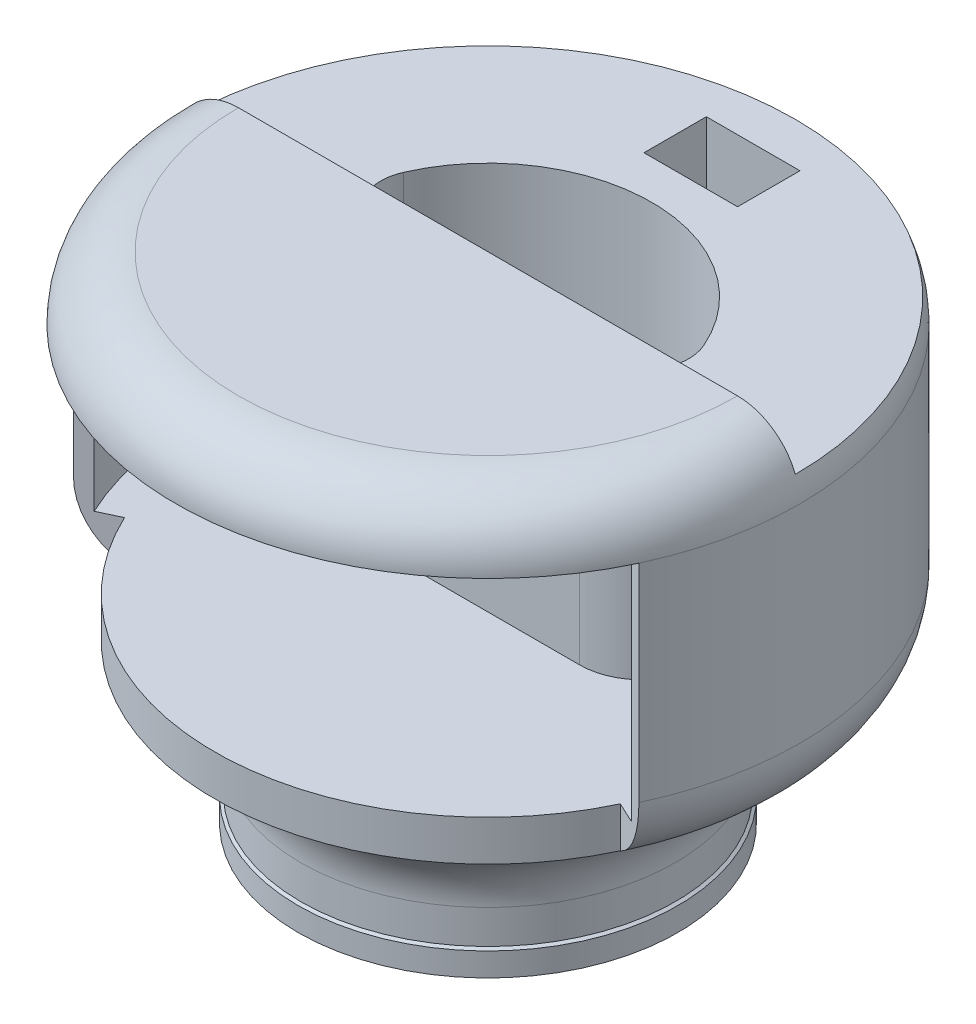
SolidWorks part; units mm, degrees
ref_plane "Front Plane" through (0, 0, 0) normal (0, 0, 1) x (1, 0, 0)
ref_plane "Top Plane" through (0, 0, 0) normal (0, 1, 0) x (1, 0, 0)
ref_plane "Right Plane" through (0, 0, 0) normal (1, 0, 0) x (0, 0, -1)
sketch "Sketch1" plane through (0, 0, 0) normal (0, 0, 1) x (1, 0, 0)
  line L0 (0, 0) -> (0, 90.2242) construction
  line L28 (0, 63.4279) -> (32, 63.4279)
  line L29 (40, 55.4279) -> (40, 28.8468)
  line L30 (22.5, 0) -> (24.35, 0)
  line L31 (24.35, 0) -> (24.35, 3)
  line L32 (24.35, 3) -> (24, 3.25)
  line L33 (24, 3.25) -> (24, 7.5811)
  line L34 (28.5399, 15.9588) -> (35.4601, 20.4691)
  line L35 (0, 13) -> (22, 13)
  line L36 (22.5, 12.5) -> (22.5, 0)
  line L37 (0, 13) -> (0, 63.4279)
  arc A0 (22, 13) -> (22.5, 12.5) centre (22, 12.5) cw
  arc A1 (24, 7.5811) -> (28.5399, 15.9588) centre (34, 7.5811) cw
  arc A2 (35.4601, 20.4691) -> (40, 28.8468) centre (30, 28.8468) ccw
  arc A3 (32, 63.4279) -> (40, 55.4279) centre (32, 55.4279) cw
  point P11 (22.9, 63.4279)
  point P18 (22.5, 13)
  point P21 (24, 13)
  point P24 (40, 23.4279)
  point P27 (40, 63.4279)
  point P28 (28.5604, 23.4279)
  point P31 (22.5, 17)
  dimension "D8" = 9.75
  dimension "D9" = 0.5
  dimension "D4" = 1.85
  dimension "D1" = 22.5
  dimension "D10" = 10
  dimension "D11" = 10
  dimension "D12" = 8
  dimension "D2" = 40
  dimension "D3" = 40
  dimension "D5" = 1.5
  dimension "D6" = 3
  dimension "D7" = 13
revolve "Revolve1" add sketch "Sketch1" angle 360 about L0
ref_plane "Plane1" through (0, 13, 0) normal (0, -1, 0) x (-1, 0, 0)
sketch "Sketch18" plane through (0, 0, 0) normal (0, 0, 1) x (1, 0, 0)
  line L0 (0, 0) -> (0, 101.5813) construction
  line L1 (-24.35, 0) -> (24.35, 0) construction
sketch "Sketch3" plane through (0, 0, 0) normal (0, 0, 1) x (1, 0, 0)
  point P0 (1.2404, 19.1989)
ref_point "Point1"
ref_plane "Plane2" through (0, 0, 22.9) normal (0, 0, 1) x (1, 0, 0)
ref_plane "Plane3" through (0, 0, 40) normal (0, 0, 1) x (1, 0, 0)
ref_plane "Plane4" through (0, 55.4279, 0) normal (0, 1, 0) x (1, 0, 0)
sketch "Sketch9" plane through (0, 55.4279, 0) normal (0, 1, 0) x (1, 0, 0)
  circle A7 centre (0, 0) radius 38
  circle A8 centre (0, 0) radius 40 construction
  circle A9 centre (0, 0) radius 23
  dimension "D1" = 2
  dimension "D2" = 46
ref_plane "Plane5" through (0, 13, 0) normal (0, -1, 0) x (-1, 0, 0)
sketch "Sketch11" plane through (0, 13, 0) normal (0, -1, 0) x (-1, 0, 0)
  line L0 (-21, 0) -> (21, 0)
  arc A1 (-21, 0) -> (21, 0) centre (0, 0) cw
  dimension "D1" = 42
extrude "Cut-Extrude3" cut sketch "Sketch11" against normal blind 60
ref_plane "Plane6" through (0, 0, -40) normal (0, 0, -1) x (-1, 0, 0)
extrude "Cut-Extrude5" cut sketch "Sketch9" against normal blind 30 and the other way blind 2
sketch "Sketch19" plane through (0, 0, 0) normal (1, 0, 0) x (0, 0, -1)
  line L0 (-47.0647, 55.4279) -> (-35.0647, 55.4279)
  line L1 (31.2976, 55.4279) -> (-31.2976, 55.4279) construction
  line L2 (-35.0647, 55.4279) -> (-35.0647, 18.9279)
  line L3 (-35.0647, 18.9279) -> (-47.0647, 18.9279)
  line L4 (-47.0647, 18.9279) -> (-47.0647, 55.4279)
  dimension "D1" = 12
  dimension "D2" = 36.5
revolve "Cut-Revolve2" cut sketch "Sketch19" angle 65 about L0 other way angle 65
ref_plane "Plane7" through (0, 0, 22.5) normal (0, 0, -1) x (-1, 0, 0)
sketch "Sketch21" plane through (0, 0, 22.5) normal (0, 0, -1) x (-1, 0, 0)
  line L0 (0, 0) -> (0, 101.5813) construction
  line L1 (-1.625, 4) -> (1.625, 4)
  line L2 (-1.625, 4) -> (-1.625, 0)
  line L3 (-1.625, 0) -> (1.625, 0)
  line L4 (1.625, 4) -> (1.625, 0)
  line L5 (-1.625, 4) -> (1.625, 0) construction
  line L6 (-1.625, 0) -> (1.625, 4) construction
  line L7 (-22.5, 0) -> (22.5, 0) construction
  point P0 (0, 2)
  dimension "D1" = 4
  dimension "D2" = 3.25
extrude "Boss-Extrude3" add sketch "Sketch21" along normal blind 1.35
pattern_circular "CirPattern1" count 5 over 360 about axis through (0, 0, 0) along (0, -1, 0) of "Boss-Extrude3"
ref_plane "Plane8" through (0, 20.4691, 0) normal (0, 1, 0) x (1, 0, 0)
sketch "Sketch22" plane through (0, 63.4279, 0) normal (0, 1, 0) x (1, 0, 0)
  line L0 (-40, 0) -> (40, 0)
  arc A0 (-40, 0) -> (40, 0) centre (0, 0) cw
  arc A1 (36.2523, -16.9047) -> (-36.2523, -16.9047) centre (0, 0) ccw construction
extrude "Cut-Extrude9" cut sketch "Sketch22" against normal blind 5
sketch "Sketch23" plane through (0, 0, -40) normal (0, 0, -1) x (-1, 0, 0)
  line L0 (0, 0) -> (0, 101.5813) construction
  line L1 (31.2976, 55.4279) -> (-31.2976, 55.4279) construction
  circle A0 centre (0, 42.1379) radius 10.5
  dimension "D1" = 21
  dimension "D2" = 13.29
extrude "Cut-Extrude10" cut sketch "Sketch23" against normal blind 10
sketch "Sketch24" plane through (0, 58.4279, 0) normal (0, 1, 0) x (1, 0, 0)
  line L1 (-8.5, 36) -> (8.5, 36)
  line L2 (-8.5, 36) -> (-8.5, 24)
  line L3 (-8.5, 24) -> (8.5, 24)
  line L4 (8.5, 36) -> (8.5, 24)
  line L5 (-8.5, 36) -> (8.5, 24) construction
  line L6 (-8.5, 24) -> (8.5, 36) construction
  arc A0 (39.4162, 0) -> (-39.4162, 0) centre (0, 0) ccw construction
  point P0 (0, 30)
  dimension "D1" = 30
  dimension "D2" = 12
  dimension "D3" = 17
extrude "Boss-Extrude4" add sketch "Sketch24" against normal blind 8
sketch "Sketch26" plane through (0, 58.4279, 0) normal (0, 1, 0) x (1, 0, 0)
  line L1 (-6, 34) -> (6, 34)
  line L2 (-6, 34) -> (-6, 26)
  line L3 (-6, 26) -> (6, 26)
  line L4 (6, 34) -> (6, 26)
  line L5 (-6, 34) -> (6, 26) construction
  line L6 (-6, 26) -> (6, 34) construction
  arc A0 (39.4162, 0) -> (-39.4162, 0) centre (0, 0) ccw construction
  point P0 (0, 30)
  dimension "D1" = 30
  dimension "D2" = 8
  dimension "D3" = 12
extrude "Cut-Extrude11" cut sketch "Sketch26" against normal blind 10
sketch "Sketch27" plane through (8.5, 0, 0) normal (1, 0, 0) x (0, 0, -1)
  line L0 (36, 50.4279) -> (36, 57.4279) construction
  line L1 (29, 56.4279) -> (33, 56.4279)
  line L2 (29, 56.4279) -> (29, 51.4279)
  line L3 (29, 51.4279) -> (33, 51.4279)
  line L4 (33, 56.4279) -> (33, 51.4279)
  line L5 (29, 56.4279) -> (33, 51.4279) construction
  line L6 (29, 51.4279) -> (33, 56.4279) construction
  line L7 (24, 50.4279) -> (24, 57.4279) construction
  line L8 (24, 50.4279) -> (36, 50.4279) construction
  point P0 (31, 53.9279)
  dimension "D1" = 12
  dimension "D2" = 3.5
  dimension "D3" = 5
  dimension "D4" = 4
  dimension "D5" = 7
extrude "Cut-Extrude12" cut sketch "Sketch27" against normal blind 5
ref_plane "Plane9" through (-39.4162, 58.4279, 0) normal (0.375, 0.927, 0) x (0.927, -0.375, 0)
ref_plane "Plane10" through (0, 58.4279, 0) normal (0, 1, 0) x (1, 0, 0)
sketch "Sketch28" plane through (0, 55.4279, 0) normal (0, 1, 0) x (1, 0, 0)
  line L0 (-22.9129, -2) -> (22.9129, -2)
  arc A0 (-22.9129, -2) -> (22.9129, -2) centre (0, 0) ccw
  dimension "D1" = 46
  dimension "D2" = 2
extrude "Cut-Extrude14" cut sketch "Sketch28" against normal blind 30 and the other way blind 2
sketch "Sketch29" plane through (0, 0, 0) normal (0, 0, -1) x (-1, 0, 0)
  line L0 (0, 0) -> (0, 101.5813) construction
  line L1 (32, 63.4279) -> (-32, 63.4279) construction
  circle A0 centre (-30.4162, 60.9279) radius 1
  circle A1 centre (30.4162, 60.9279) radius 1
  circle A2 centre (0, 60.9279) radius 1
  dimension "D1" = 2
  dimension "D2" = 2
  dimension "D3" = 2
  dimension "D4" = 2.5
  dimension "D5" = 2.5
  dimension "D6" = 2.5
  dimension "D7" = 9
  dimension "D8" = 9
extrude "Cut-Extrude15" cut sketch "Sketch29" against normal blind 15
fillet "Fillet1" radius 6 2 edges at (-21, 35.7139, 0) (21, 35.7139, 0)
fillet "Fillet2" radius 8 2 edges at (22.9129, 41.4279, 2) (-22.9129, 41.4279, 2)
